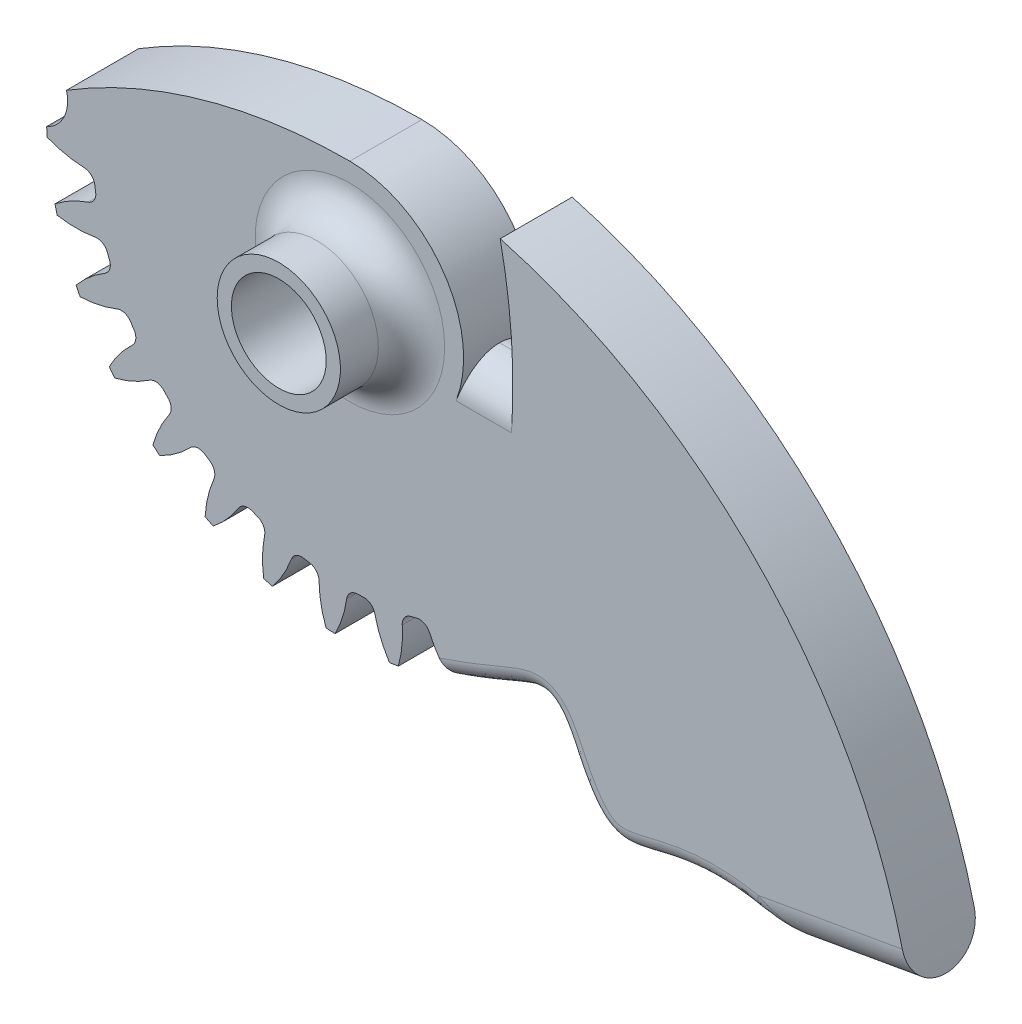
SolidWorks part; units mm, degrees
material "ABS"
ref_plane "Front" through (0, 0, 0) normal (0, 0, 1) x (1, 0, 0)
ref_plane "Top" through (0, 0, 0) normal (0, 1, 0) x (1, 0, 0)
ref_plane "Right" through (0, 0, 0) normal (1, 0, 0) x (0, 0, -1)
sketch "Sketch3" plane through (0, 0, 0) normal (0, 0, 1) x (1, 0, 0)
  circle A0 centre (0, 0) radius 40.64
  dimension "od" = 40.64
extrude "gearBody" add sketch "Sketch3" along normal blind 9.652
sketch "Sketch2" plane through (0, 0, 0) normal (0, 0, 1) x (1, 0, 0)
  line L0 (0, 0) -> (34.0786, 14.1158) construction
  line L1 (45.4751, -11.4855) -> (0, 0) construction
  line L2 (0, 0) -> (36.3143, 0) construction
  line L3 (38.0972, -0.458) -> (37.8451, -4.4001) construction
  line L5 (37.9712, -2.4291) -> (0, 0) construction
  line L7 (0, 0) -> (36.8864, 0) construction
  arc A0 (36.879, -0.7403) -> (36.6727, -3.9649) centre (0, 0) ccw construction
  arc A1 (40.637, 0.4947) -> (40.2427, -5.6687) centre (0, 0) ccw construction
  arc A2 (38.0972, -0.458) -> (37.8451, -4.4001) centre (0, 0) ccw construction
  arc A3 (34.9015, -2.6404) -> (34.9534, -1.8283) centre (0, 0) ccw construction
  arc A4 (45.4751, -11.4855) -> (35.6466, -3.6712) centre (32.0022, -18.3431) ccw construction
  arc A5 (45.4751, -11.4855) -> (46.5679, 5.5974) centre (0, 0) ccw construction
  arc A6 (46.5679, 5.5974) -> (35.8238, -0.9008) centre (34.0786, 14.1158) cw construction
  arc A7 (34.9534, -1.8283) -> (35.8238, -0.9008) centre (35.9376, -1.8798) cw construction
  arc A8 (35.6466, -3.6712) -> (34.9015, -2.6404) centre (35.8842, -2.7147) cw construction
  arc A9 (46.8801, 7.0756) -> (35.7652, -0.3962) centre (34.0786, 14.1158) cw
  arc A10 (34.4461, -1.8018) -> (35.7652, -0.3962) centre (35.9376, -1.8798) cw
  arc A11 (34.3949, -2.6021) -> (34.4461, -1.8018) centre (0, 0) ccw
  arc A12 (35.5241, -4.1642) -> (34.3949, -2.6021) centre (35.8842, -2.7147) cw
  arc A13 (45.5964, -12.9914) -> (35.5241, -4.1642) centre (32.0022, -18.3431) ccw
  arc A14 (45.5964, -12.9914) -> (46.8801, 7.0756) centre (0, 0) ccw
  point P6 (46.5679, 5.5974)
  point P22 (45.4751, -11.4855)
  dimension "D1" = 0.508
  dimension "baseDia" = 73.7729
  dimension "od" = 81.28
  dimension "pd" = 76.2
  dimension "rd" = 70.0024
  dimension "rFillet" = 0.9855
  dimension "pointX" = 46.5679
  dimension "pointY" = 5.5974
  dimension "CTT" = 3.9421
  dimension "flankCenterAngle" = 22.5
extrude "toothCut" cut sketch "Sketch2" along normal through all
pattern_circular "CirPattern1" count 30 over 360 about axis through (0, 0, 9.652) along (0, 0, -1) of "toothCut"
sketch "hub1Dia" plane through (0, 0, 0) normal (0, 0, -1) x (-1, 0, 0)
  circle A0 centre (0, 0) radius 12.7
  dimension "hub1Dia" = 25.4
sketch "hub2Dia" plane through (0, 0, 9.652) normal (0, 0, 1) x (1, 0, 0)
  circle A0 centre (0, 0) radius 12.7
  dimension "hub2dia" = 25.4
sketch "boreDia" plane through (0, 0, 0) normal (0, 0, 1) x (1, 0, 0)
  circle A0 centre (0, 0) radius 6.7469
  dimension "boreDia" = 13.4937
extrude "bore" cut sketch "boreDia" against normal mid plane 25400
sketch "Sketch4" plane through (0, 0, 9.652) normal (0, 0, 1) x (1, 0, 0)
  circle A0 centre (0, -57.15) radius 76.1746
  arc A2 (-41.7195, 6.5842) -> (41.7195, 6.5842) centre (0, 0) cw
  dimension "D1" = 152.3492
  dimension "D2" = 57.15
extrude "Cut-Extrude1" cut sketch "Sketch4" against normal through all contours A0 region at (0, 26.0638, 9.652)
sketch "Sketch5" plane through (0, 0, 9.652) normal (0, 0, 1) x (1, 0, 0)
  line L0 (0, 19.0246) -> (21.5163, 3.7176)
  line L1 (21.5163, 3.7176) -> (10.4433, -33.7781)
  line L2 (10.4433, -33.7781) -> (13.558, -38.3117)
  line L3 (0, 0) -> (0, -57.15) construction
  line L4 (0, -57.15) -> (-54.1615, -3.586) construction
  line L5 (0, -57.15) -> (65.9691, -95.2373) construction
  line L9 (0, -57.15) -> (75.0173, -43.9224) construction
  line L12 (60.232, -46.5295) -> (75.0173, -43.9224)
  line L13 (0, -57.15) -> (29.696, -40.005) construction
  line L14 (29.696, -40.005) -> (26.521, -34.5057) construction
  circle A1 centre (0, -57.15) radius 76.1746 construction
  arc A5 (0, 19.0246) -> (75.0173, -43.9224) centre (0, -57.15) cw
  circle A6 centre (0, -57.15) radius 21.59 construction
  arc A9 (10.6752, -34.1372) -> (8.9309, -33.317) centre (9.3176, -34.7596) ccw construction
  circle A12 centre (49.4934, -85.725) radius 40.64 construction
  spline S0 degree 3 poles (13.558, -38.3117) (21.087, -35.7646) (26.3659, -31.8249) (36.3578, -56.1686) (39.5345, -39.0169) (60.232, -46.5295) knots 0 0 0 0 0.118515 0.218515 1 1 1 1
  point P28 (21.569, -56.1981)
  dimension "D1" = 43.18
  dimension "D3" = 81.28
  dimension "D6" = 152.3492
  dimension "D2" = 120
  dimension "D4" = 57.15
  dimension "D8" = 57.15
  dimension "D7" = 60
  dimension "D9" = 34.29
  dimension "D10" = 6.35
  dimension "D5" = 80
extrude "Boss-Extrude1" add sketch "Sketch5" against normal up to surface (9.652 mm away) up to face at (6.7469, 0, 0)
sketch "Sketch6" plane through (0, 0, 9.652) normal (0, 0, 1) x (1, 0, 0)
  line L1 (-41.2993, 3.0747) -> (-42.3397, 6.1739)
  line L2 (15.875, 0) -> (21.209, 0)
  circle A0 centre (0, -57.15) radius 76.1746 construction
  arc A1 (75.0173, -43.9224) -> (-33.55, 11.2383) centre (0, -57.15) ccw construction
  circle A2 centre (0, 0) radius 15.875 construction
  arc A3 (0, 15.875) -> (15.875, 0) centre (0, 0) cw
  arc A4 (19.4523, 16.499) -> (-42.3397, 6.1739) centre (0, -57.15) ccw
  arc A5 (0, 15.875) -> (-41.2993, 3.0747) centre (0, -57.15) ccw
  circle A6 centre (0, 0) radius 21.209 construction
  circle A8 centre (-57.15, 0) radius 78.359 construction
  arc A9 (21.209, 0) -> (19.4523, 16.499) centre (-57.15, 0) ccw
  dimension "D4" = 57.15
  dimension "D1" = 31.75
  dimension "D2" = 42.418
  dimension "D3" = 156.718
extrude "Cut-Extrude2" cut sketch "Sketch6" against normal through all
sketch "Sketch7" plane through (0, 0, 9.652) normal (0, 0, 1) x (1, 0, 0)
  circle A0 centre (0, 0) radius 6.7469
  circle A1 centre (0, 0) radius 6.7469 construction
  circle A2 centre (0, 0) radius 8.255
  dimension "D1" = 16.51
extrude "spacer" add sketch "Sketch7" along normal blind 9.525
fillet "Fillet1" radius 4.445 1 edges at (8.255, 0, 9.652)
sketch "Sketch8" plane through (0, 0, 9.652) normal (0, 0, 1) x (1, 0, 0)
  line L0 (-38.1756, 5.1017) -> (-34.0224, 5.3247)
  line L1 (-34.0224, 5.3247) -> (-34.2899, 0.0545)
  line L2 (-34.2899, 0.0545) -> (-40.6263, -1.0555)
  arc A0 (-38.1756, 5.1017) -> (-40.6263, -1.0555) centre (-42.6187, 3.3039) cw
extrude "overextension stop" add sketch "Sketch8" against normal up to surface (9.652 mm away) up to face at (-13.508, -22.4485, 0)
sketch "Sketch11" plane through (0, 0, 9.652) normal (0, 0, 1) x (1, 0, 0)
  line L3 (15.2268, -0.635) -> (21.8414, -0.635)
  line L4 (15.2268, -0.635) -> (21.8414, -0.635)
  line L6 (-37.9725, 4.4812) -> (-39.287, 5.4618)
  line L7 (-39.287, 5.4618) -> (-10.5387, 26.6943)
  line L8 (-10.5387, 26.6943) -> (20.0731, 16.6327)
  arc A5 (-40.3928, -0.941) -> (-38.1756, 5.1017) centre (-42.6187, 3.3039) ccw construction
  arc A6 (15.2268, -0.635) -> (0, 15.24) centre (0, 0) ccw
  arc A7 (21.8414, -0.635) -> (20.0731, 16.6327) centre (-57.15, 0) ccw
  arc A8 (15.2268, -0.635) -> (0, 15.24) centre (0, 0) ccw
  arc A9 (21.8414, -0.635) -> (20.0731, 16.6327) centre (-57.15, 0) ccw
  arc A10 (0, 15.24) -> (-37.8436, 4.5604) centre (0, -57.15) ccw
  arc A11 (0, 15.24) -> (-37.9725, 4.4812) centre (0, -57.15) ccw
  point P0 (-39.287, 5.4618)
  dimension "D1" = 0.635
  dimension "D2" = 0.635
extrude "Cut-Extrude3" cut sketch "Sketch11" against normal through all
sketch "Sketch10" plane through (0, 0, 9.652) normal (0, 0, 1) x (1, 0, 0)
  circle A0 centre (0, 0) radius 6.35
  circle A1 centre (0, 0) radius 7.3025
  dimension "D1" = 12.7
  dimension "D2" = 14.605
extrude "bore dia" add sketch "Sketch10" along normal up to surface and the other way up to surface up to face at (8.255, 0, 19.177) other way up to face at (-12.6074, -23.7153, 0)
fillet "Fillet4" radius 4.826 4 edges at (18.5341, -0.635, 0) (18.5341, -0.635, 9.652) (67.6247, -45.2259, 0) (67.6247, -45.2259, 9.652)
fillet "Fillet3" radius 2.286 4 edges at (56.6479, -45.3986, 8.5331) (54.7143, -44.9405, 0.585)
equation "\"Bodytube_OD\"= 6.17in"
equation "\"Bodytube_ID\"= 5.998in"
equation "\"Fwd_Tube_Length\"= 40in"
equation "\"Mid_Tube_Length\"= 1in"
equation "\"Aft_Section_Length\"= 39in"
equation "\"Mid_Coupler_Length\"= 13in"
equation "\"Aft_Lower_Length\"= 22in"
equation "\"AB_Coupler_OD_Length\"= 1in"
equation "\"AB_Coupling_Section_Length\"= 0.375in"
equation "\"AB_Coupler_Length\"= \"AB_Coupler_OD_Length\" + \"AB_Coupling_Section_Length\" * 2"
equation "\"Cutout_Angle\"= 80"
equation "\"AB_Paddle_Height\"= 0.375in"
equation "\"AB_Coupler_Num_Screws\"= 4"
equation "\"Num_Cutouts\"= 3"
equation "\"AB_Coupler_OD\"= 6.17in"
equation "\"AB_Coupler_ID\"= 5.75in"
equation "\"AB_Coupler_Surface_Diameter\"= 5.998in"
equation "\"AB_Coupling_Screw_Diameter\"= 0.15748in"
equation "\"AB_Central_Bushing_Length\"= .4724in"
equation "\"Lead_Screw_Dist\"= 3.4in"
equation "\"Lead_Screw_Diam\"= 0.386in"
equation "\"Lead_Screw_Length\"= (\"Mid_Coupler_Length\" + 2*0.375in + 2*0.5in)"
equation "\"Paddle_Pin_Offset\"= .25in"
equation "\"Paddle_Pin_Radius\"= 2.25in"
equation "\"Fwd_BKHD_From_Top\"= 18in"
equation "\"D1@Sketch4\"=\"Bodytube_ID\""
equation "\"D2@Sketch4\"=\"Paddle_Pin_Radius\""
equation "\"D3@Sketch5\"=\"Paddle_Gear_OD\""
equation "\"D4@Sketch5\"=\"Paddle_Pin_Radius\""
equation "\"Motor_OD\"= 4in"
equation "\"Aft_Upper_Length\"= \"Aft_Section_Length\" - \"Aft_Lower_Length\" - \"AB_Coupler_OD_Length\""
equation "\"Paddle_Gear_OD\"= 3.2in"
equation "\"D5@Sketch5\"=\"Cutout_Angle\""
equation "\"D6@Sketch5\"=\"Bodytube_ID\""
equation "\"D1@Sketch6\"=\"AB_Coupler_ID\"-2*\"Paddle_Pin_Radius\""
equation "\"D2@Sketch6\"=\"Bodytube_OD\"-2*\"Paddle_Pin_Radius\""
equation "\"D3@Sketch6\"=\"Bodytube_OD\""
equation "\"D4@Sketch6\"=\"Paddle_Pin_Radius\""
equation "\"D8@Sketch5\"=\"Paddle_Pin_Radius\""
equation "\"Drive_Gear_OD\"= 1.7in"
equation "\"Fin_Thickness\"= .118in"
equation "\"Guiderail_Cutout_Diameter\"= 1.5in"
equation "\"DB9_Hole_Dist\"= 25mm"
equation "\"D1@Sketch5\"=\"Drive_Gear_OD\""
